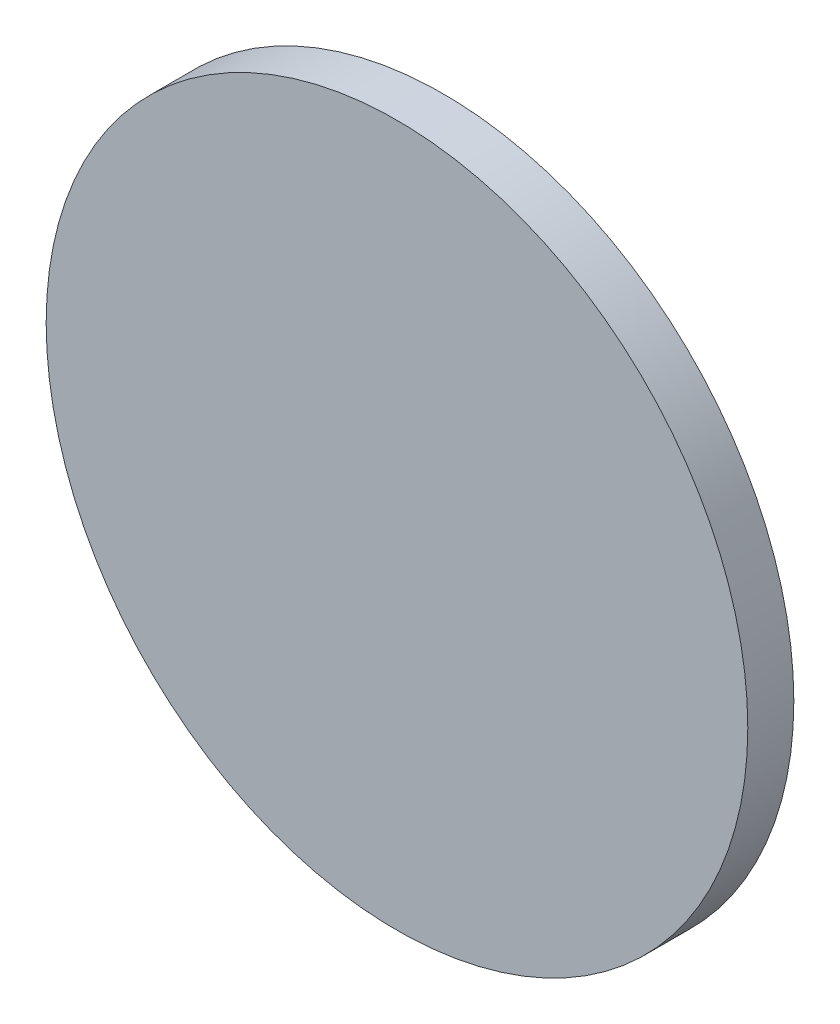
SolidWorks part; units mm, degrees
ref_plane "Front Plane" through (0, 0, 0) normal (0, 0, 1) x (1, 0, 0)
ref_plane "Top Plane" through (0, 0, 0) normal (0, 1, 0) x (1, 0, 0)
ref_plane "Right Plane" through (0, 0, 0) normal (1, 0, 0) x (0, 0, -1)
sketch "Sketch1" plane through (0, 0, 0) normal (0, 0, 1) x (1, 0, 0)
  circle A0 centre (0, 0) radius 76.2
  dimension "D1" = 152.4
extrude "Boss-Extrude1" add sketch "Sketch1" along normal mid plane 10
